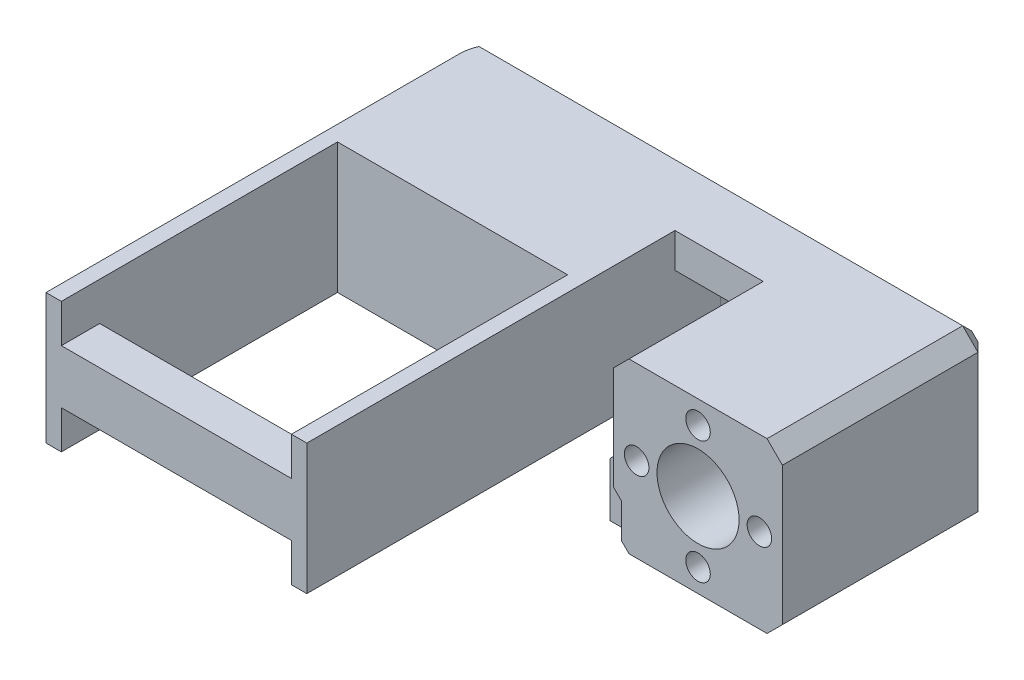
SolidWorks part; units mm, degrees
ref_plane "Płaszczyzna przednia" through (0, 0, 0) normal (0, 0, 1) x (1, 0, 0)
ref_plane "Płaszczyzna górna" through (0, 0, 0) normal (0, 1, 0) x (1, 0, 0)
ref_plane "Płaszczyzna prawa" through (0, 0, 0) normal (1, 0, 0) x (0, 0, -1)
sketch "Szkic2" plane through (0, 0, 0) normal (0, 1, 0) x (1, 0, 0)
  line L0 (0, 0) -> (0, 11.0602) construction
  line L5 (17, 19) -> (-17, 19)
  line L6 (17, 19) -> (17, -19)
  line L11 (17, -19) -> (-17, -19)
  line L12 (-17, 19) -> (-17, -19)
  line L13 (17, 19) -> (-17, -19) construction
  line L14 (17, -19) -> (-17, 19) construction
  line L16 (15, 17) -> (-15, 17)
  line L17 (15, 17) -> (15, -14)
  line L18 (15, -14) -> (-15, -14)
  line L19 (-15, 17) -> (-15, -14)
  line L20 (15, 17) -> (-15, -14) construction
  line L21 (15, -14) -> (-15, 17) construction
  point P0 (0, 0)
  point P5 (0, 1.5)
  dimension "D1" = 34
  dimension "D2" = 38
  dimension "D3" = 2
  dimension "D4" = 2
  dimension "D5" = 5
extrude "Dodanie-wyciągnięcie1" add sketch "Szkic2" along normal blind 17
sketch "Szkic6" plane through (0, 0, 14) normal (0, 0, -1) x (-1, 0, 0)
  line L0 (0, 17) -> (0, 0) construction
  line L1 (15, 17) -> (-15, 17) construction
  line L2 (15, 0) -> (-15, 0) construction
  line L3 (-15, 17) -> (-15, 0) construction
  line L4 (15, 5) -> (-15, 5)
  line L5 (15, 5) -> (15, 12)
  line L6 (15, 12) -> (-15, 12)
  line L7 (-15, 5) -> (-15, 12)
  line L8 (15, 5) -> (-15, 12) construction
  line L9 (15, 12) -> (-15, 5) construction
  line L11 (-15, 17) -> (15, 17)
  line L12 (-15, 17) -> (-15, 0)
  line L13 (-15, 0) -> (15, 0)
  line L14 (15, 17) -> (15, 0)
  point P6 (0, 8.5)
  line M9 (-15, 0) -> (15, 0)
  line M10 (15, 0) -> (15, 17)
  line M11 (15, 17) -> (-15, 17)
  line M12 (-15, 17) -> (-15, 0)
  dimension "D1" = 5
extrude "Wytnij-wyciągnięcie1" cut sketch "Szkic6" against normal blind 17 contours L6 M10 M11 M12 | L4 M10 M12 M9 region at (0, 2.5, 14) region at (0, 14.5, 14)
sketch "Szkic7" plane through (0, 0, -19) normal (0, 0, -1) x (-1, 0, 0)
  line L1 (-17, 17) -> (17, 17)
  line L2 (-17, 17) -> (-17, 0)
  line L3 (-17, 0) -> (17, 0)
  line L4 (17, 17) -> (17, 0)
extrude "Dodanie-wyciągnięcie2" add sketch "Szkic7" along normal blind 10
sketch "Szkic8" plane through (0, 0, -29) normal (0, 0, -1) x (-1, 0, 0)
  line L0 (-17, 17) -> (-17, 18) construction
  line L1 (-17, 17) -> (-24, 17)
  line L2 (-17, 17) -> (-17, 12.5)
  line L3 (-17, 12.5) -> (-24, 12.5)
  line L4 (-24, 17) -> (-24, 12.5)
  line L5 (-17, 17) -> (17, 17)
  line L6 (-17, 17) -> (-17, 0)
  line L7 (-17, 0) -> (17, 0)
  line L8 (17, 17) -> (17, 0)
  line L9 (-17, 18) -> (-22.5, 18) construction
  line L10 (-37.5, 18) -> (-37.5, -6) construction
  line L11 (-22.5, 18) -> (-52.5, 18) construction
  line L12 (-24, 17) -> (-37.5, 17)
  line L13 (-24, 12.5) -> (-26.9837, 2.7739)
  circle A0 centre (-37.5, 6) radius 5.35
  circle A1 centre (-37.5, 6) radius 11
  line M16 (-17, 17) -> (-17, 0)
  line M17 (-17, 0) -> (17, 0)
  line M18 (17, 0) -> (17, 17)
  line M19 (17, 17) -> (-17, 17)
  dimension "D6" = 10.7
  dimension "D1" = 4.5
  dimension "D2" = 7
  dimension "D3" = 5.5
  dimension "D4" = 1
  dimension "D5" = 24
  dimension "30" = 30
extrude "Dodanie-wyciągnięcie3" add sketch "Szkic8" along normal blind 10 contours A1 A0 | A1 L13 L4 L12 | L1 L4 L3 M16 | M19 M16 M17 M18 region at (20.5, 14.75, -29) region at (0, 8.5, -29) region at (27.368, 13.5434, -29) region at (29.9418, 13.5582, -29)
sketch "Szkic10" plane through (0, 0, -29) normal (0, 0, 1) x (1, 0, 0)
  circle A0 centre (37.5, 6) radius 5.35
  circle A1 centre (37.5, 6) radius 11
extrude "Dodanie-wyciągnięcie4" add sketch "Szkic10" along normal blind 17.5
sketch "Szkic11" plane through (0, 0, -39) normal (0, 0, -1) x (-1, 0, 0)
  circle A0 centre (-37.5, 6) radius 4.2
  circle A1 centre (-37.5, 6) radius 5.35
  dimension "D1" = 8.4
extrude "Dodanie-wyciągnięcie5" add sketch "Szkic11" against normal blind 16
sketch "Szkic13" plane through (0, 0, -11.5) normal (0, 0, 1) x (1, 0, 0)
  line L0 (37.5, 6) -> (37.5, 14) construction
  circle A0 centre (37.5, 6) radius 8
  circle A1 centre (37.5, 14) radius 1.6
  circle A2 centre (45.5, 6) radius 1.6
  circle A3 centre (37.5, -2) radius 1.6
  circle A4 centre (29.5, 6) radius 1.6
  point P16 (37.5, 6)
  dimension "D3" = 3.2
  dimension "D1" = 8
  dimension "D2" = 4
extrude "Wytnij-wyciągnięcie2" cut sketch "Szkic13" against normal blind 10 contours A0 A4 | A0 A4 | A1 L0 A0 | A0 A1 | L0 A1 A0 | A0 A2 | A0 A2 | A0 A3 | A0 A3 region at (36.844, 13.2929, -11.5) region at (38.156, 13.2929, -11.5) region at (37.5, 14.6494, -11.5) region at (30.2071, 6, -11.5) region at (28.8506, 6, -11.5) region at (46.1494, 6, -11.5) region at (44.7929, 6, -11.5) region at (37.5, -1.2929, -11.5) region at (37.5, -2.6494, -11.5)
sketch "Szkic16" plane through (0, 0, -39) normal (0, 0, -1) x (-1, 0, 0)
  line L0 (17, 17) -> (-37.5, 17) construction
  line L1 (-26.5, 17) -> (-48.5, 17)
  line L2 (-26.5, 17) -> (-26.5, -5)
  line L3 (-26.5, -5) -> (-48.5, -5)
  line L4 (-48.5, 17) -> (-48.5, -5)
  line L5 (-26.5, 17) -> (-48.5, -5) construction
  line L6 (-26.5, -5) -> (-48.5, 17) construction
  arc A0 (-37.5, 17) -> (-26.9837, 2.7739) centre (-37.5, 6) ccw construction
  circle A1 centre (-37.5, 6) radius 11
  point P0 (-37.5, 6)
  arc M5 (-37.5, 17) -> (-26.9837, 2.7739) centre (-37.5, 6) ccw
  line M6 (-26.9837, 2.7739) -> (-24, 12.5)
  line M11 (17, 17) -> (-37.5, 17)
extrude "Dodanie-wyciągnięcie6" add sketch "Szkic16" against normal up to surface (27.5 mm away) contours L1 L4 M5 | A1 L2 M11 | L3 L2 M6 M5 | L4 L3 M5 | A1 L2 M6 region at (28.957, 14.543, -39) region at (46.043, 14.543, -39) region at (26.5971, 4.3652, -39) region at (46.043, -2.543, -39) region at (28.9693, -2.5788, -39) up to face at (31.1, 6, -11.5)
chamfer "Sfazowanie1" distance 2 angle 45 4 edges at (26.5, -5, -25.25) (48.5, -5, -25.25) (26.5, 17, -20.25) (48.5, 17, -25.25)
chamfer "Sfazowanie2" distance 2 angle 45 3 edges at (17, 6.25, -39) (0, 0, -39) (-17, 8.5, -39)
chamfer "Sfazowanie3" distance 2 angle 45 9 edges at (19.5, 12.5, -39) (15.75, 17, -39) (47.5, 16, -39) (48.5, 6, -39) (47.5, -4, -39) (37.5, -5, -39) (27.5, -4, -39) (26.5, 0.6753, -39) (25.25, 8.4253, -39)
fillet "Zaokrąglenie1" radius 5 2 edges at (17, 6.25, -37) (-17, 8.5, -37)
ref_plane "Płaszczyzna1" through (0, 0, -19) normal (0, 0, 1) x (1, 0, 0)
sketch "Szkic18" plane through (0, 0, -19) normal (0, 0, 1) x (1, 0, 0)
  line L0 (28.5, 17) -> (23.5, 17)
  line L1 (23.5, 2) -> (26.5, 2)
  line L2 (17, 17) -> (28.5, 17) construction
  line L3 (23.5, 17) -> (23.5, -5)
  line L4 (23.5, -5) -> (28.5, -5)
  line L6 (26.5, 15) -> (26.5, -3) construction
  line L7 (26.5, -3) -> (28.5, -5) construction
  line L8 (28.5, 17) -> (26.5, 15) construction
  line L9 (26.5, -3) -> (28.5, -5)
  line L10 (26.5, 15) -> (26.5, -3)
  line L11 (28.5, 17) -> (26.5, 15)
  dimension "D1" = 3
  dimension "D2" = 7
extrude "Dodanie-wyciągnięcie8" add sketch "Szkic18" along normal blind 5 contours L10 L3 L4 L9 region at (25.1884, -1.7464, -19)
sketch "Szkic19" plane through (0, 0, -14) normal (0, 0, 1) x (1, 0, 0)
  line L1 (23.5, -5) -> (27.5, -5)
  line L2 (23.5, -5) -> (23.5, 0.5)
  line L3 (23.5, 0.5) -> (27.5, 0.5)
  line L4 (27.5, -5) -> (27.5, 0.5)
  dimension "D1" = 4
  dimension "D2" = 5.5
extrude "Wytnij-wyciągnięcie3" cut sketch "Szkic19" along normal blind 6
sketch "Szkic20" plane through (0, 0, -19) normal (0, 0, -1) x (-1, 0, 0)
  line L7 (-28.5, -5) -> (-23.5, -5)
  line L8 (-27.5, -4) -> (-28.5, -5)
  line L9 (-27.5, 0.5) -> (-27.5, -4)
  line L10 (-26.5, 0.5) -> (-27.5, 0.5)
  line L11 (-26.5, 2) -> (-26.5, 0.5)
  line L12 (-23.5, 2) -> (-26.5, 2)
  line L13 (-23.5, -5) -> (-23.5, 2)
  line L14 (-28.5, -5) -> (-23.5, -5)
  line L15 (-27.5, -4) -> (-28.5, -5)
  line L16 (-27.5, 0.5) -> (-27.5, -4)
  line L17 (-26.5, 0.5) -> (-27.5, 0.5)
  line L18 (-26.5, 2) -> (-26.5, 0.5)
  line L20 (-23.5, -5) -> (-23.5, 2)
  line L21 (-23.5, 2) -> (-26.5, 2)
  dimension "D1" = 0
extrude "Wytnij-wyciągnięcie4" cut sketch "Szkic20" along normal blind 26
chamfer "Sfazowanie4" distance 1 angle 45 2 edges at (26.5, 0.5, -28) (26.5, 0.5, -12.75)
chamfer "Sfazowanie5" distance 3 angle 45 1 edges at (26.5, 2, -16.5)
chamfer "Sfazowanie6" distance 1 angle 45 2 edges at (33.3, 6, -23) (33.3, 6, -39)
